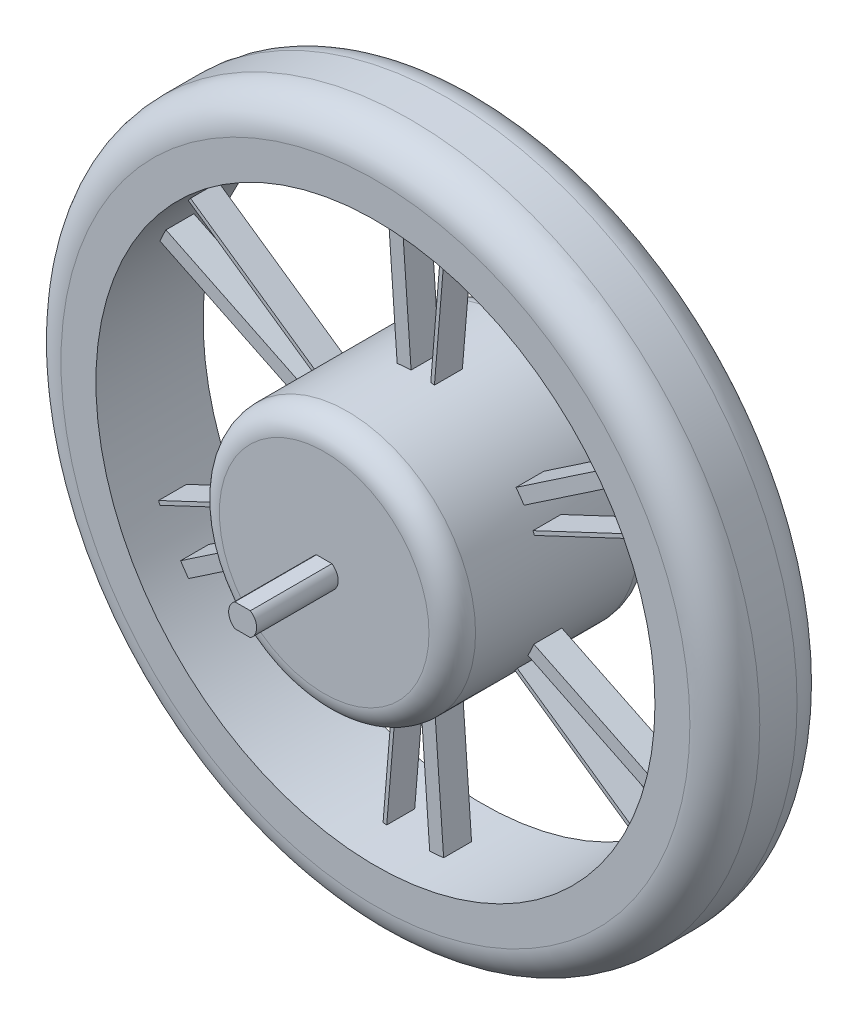
SolidWorks part; units mm, degrees
ref_plane "Front Plane" through (0, 0, 0) normal (0, 0, 1) x (1, 0, 0)
ref_plane "Top Plane" through (0, 0, 0) normal (0, 1, 0) x (1, 0, 0)
ref_plane "Right Plane" through (0, 0, 0) normal (1, 0, 0) x (0, 0, -1)
sketch "Sketch1" plane through (0, 0, 0) normal (0, 0, 1) x (1, 0, 0)
  circle A0 centre (0, 0) radius 55
  dimension "D1" = 110
extrude "Boss-Extrude1" add sketch "Sketch1" along normal mid plane 90
sketch "Sketch2" plane through (0, 0, 0) normal (0, 0, 1) x (1, 0, 0)
  circle A0 centre (0, 0) radius 150
  circle A1 centre (0, 0) radius 120
  dimension "D1" = 300
  dimension "D2" = 30
extrude "Boss-Extrude2" add sketch "Sketch2" along normal mid plane 46 separate body
sketch "Sketch3" plane through (0, 0, 0) normal (0, 0, 1) x (1, 0, 0)
  line L0 (-6.293, 119.8349) -> (-1.6905, 54.974)
  line L3 (-12.2751, 119.3705) -> (-7.6693, 54.4627)
  line L4 (13.7244, 119.2126) -> (8.3304, 54.3655)
  line L5 (6.7528, 54.5839) -> (12.1429, 119.384)
  circle A0 centre (0, 0) radius 55 construction
  circle A1 centre (0, 0) radius 120 construction
  arc A8 (13.7244, 119.2126) -> (12.1429, 119.384) centre (0, 0) ccw
  arc A9 (8.3304, 54.3655) -> (6.7528, 54.5839) centre (0, 0) ccw
  arc A10 (-6.293, 119.8349) -> (-12.2751, 119.3705) centre (0, 0) ccw
  arc A11 (-1.6905, 54.974) -> (-7.6693, 54.4627) centre (0, 0) ccw
  dimension "D1" = 26
  dimension "D2" = 6
  dimension "D3" = 16
extrude "Boss-Extrude3" add sketch "Sketch3" along normal mid plane 12
ref_axis "Axis2" through (0, 0, -53.35) along (0, 0, 1)
pattern_circular "CirPattern15" count 6 over 360 about axis through (0, 0, -53.35) along (0, 0, 1) of "Boss-Extrude3"
fillet "Fillet1" radius 15 2 edges at (150, 0, -23) (150, 0, 23)
sketch "Sketch5" plane through (0, 0, 45) normal (0, 0, 1) x (1, 0, 0)
  line L0 (-3.3166, 5) -> (3.3166, 5)
  line L1 (-3.3166, -5) -> (3.3166, -5)
  arc A0 (-3.3166, 5) -> (-3.3166, -5) centre (0, 0) ccw
  arc A1 (3.3166, -5) -> (3.3166, 5) centre (0, 0) ccw
  dimension "D1" = 12
  dimension "D2" = 10
extrude "Boss-Extrude4" add sketch "Sketch5" along normal blind 35
mirror "Mirror1" about plane through (0, 0, 0) normal (0, 0, 1) of "Boss-Extrude4"
fillet "Fillet2" radius 10 2 edges at (55, 0, 45) (55, 0, -45)
